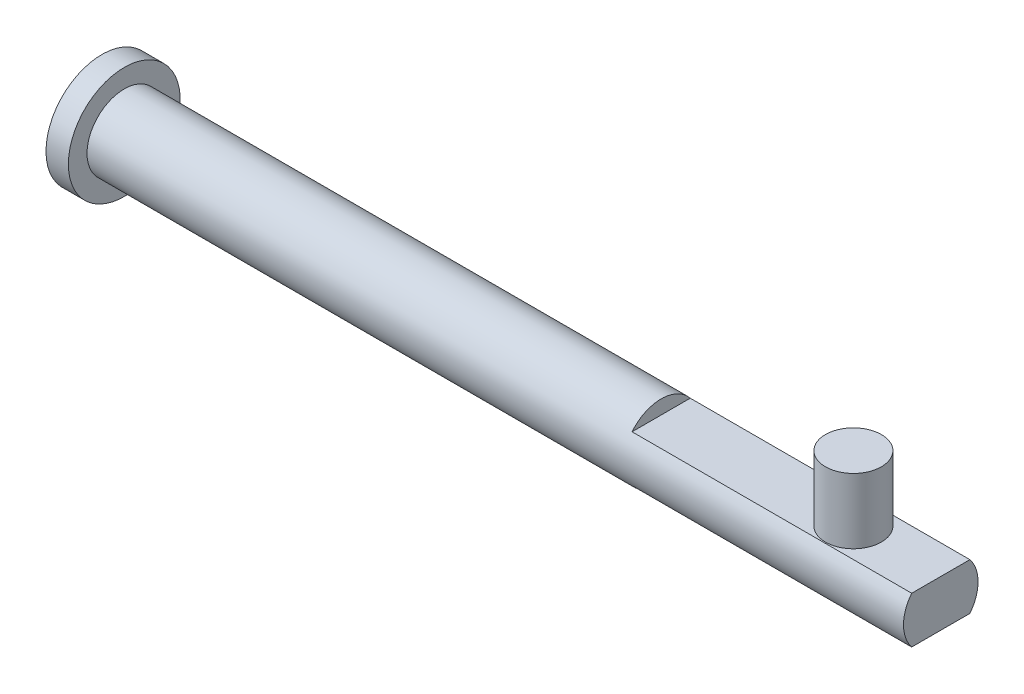
SolidWorks part; units mm, degrees
ref_plane "Front Plane" through (0, 0, 0) normal (0, 0, 1) x (1, 0, 0)
ref_plane "Top Plane" through (0, 0, 0) normal (0, 1, 0) x (1, 0, 0)
ref_plane "Right Plane" through (0, 0, 0) normal (1, 0, 0) x (0, 0, -1)
sketch "Sketch1" plane through (0, 0, 0) normal (0, 1, 0) x (1, 0, 0)
  line L0 (57.7358, -1.8) -> (57.7358, 6.2)
  line L1 (57.7358, 6.2) -> (-117.4647, 6.2)
  line L3 (-122.2642, -1.8) -> (57.7358, -1.8)
  line L4 (-117.4647, 6.2) -> (-117.4647, 10.2)
  line L5 (-117.4647, 10.2) -> (-122.2642, 10.2)
  line L6 (-122.2642, -1.8) -> (-122.2642, 10.2)
  point P3 (0, 0)
  dimension "D1" = 8
  dimension "D2" = 12
revolve "Revolve1" add sketch "Sketch1" angle 360 about L3
ref_axis "Axis1" through (57.7358, 0, 1.8) along (-1, 0, 0)
sketch "Sketch4" plane through (57.7358, 0, 0) normal (1, 0, 0) x (0, 0, -1)
  line L1 (12.1992, 5) -> (-21.7258, 5)
  line L2 (12.1992, 5) -> (12.1992, -5)
  line L3 (12.1992, -5) -> (-21.7258, -5)
  line L4 (-21.7258, 5) -> (-21.7258, -5)
  dimension "D1" = 5
  dimension "D2" = 10
extrude "Cut-Extrude1" cut sketch "Sketch4" against normal blind 60 flip side to cut
sketch "Sketch9" plane through (0, 5, 0) normal (0, 1, 0) x (1, 0, 0)
  line L0 (57.7358, -1.8) -> (-117.4647, -1.8) construction
  circle A1 centre (38.9858, -1.8) radius 6
  point P0 (38.9858, -1.8)
  dimension "D2" = 12
extrude "Boss-Extrude1" add sketch "Sketch9" along normal blind 14 contours A1
equation "\"RAYON_AXE\" = 8"
equation "\"D1@Sketch1\"=\"RAYON_AXE\""
equation "\"LONGUEUR_AXE\"= 180"
equation "\"PIVOT_LINK_THICNESS\"=5"
equation "\"D2@Sketch4\"=\"PIVOT_LINK_THICNESS\"*2"
equation "\"PIVOT_LINK_LENGTH\"= 60"
equation "\"D1@Cut-Extrude1\"=\"PIVOT_LINK_LENGTH\""
equation "\"DOWL_LENGTH\"=14"
equation "\"D1@Boss-Extrude1\"=\"DOWL_LENGTH\""
equation "\"D2@Sketch1\"=\"RAYON_AXE\"+4"
equation "\"D2@Sketch9\"=\"RAYON_AXE\"*2-4"
